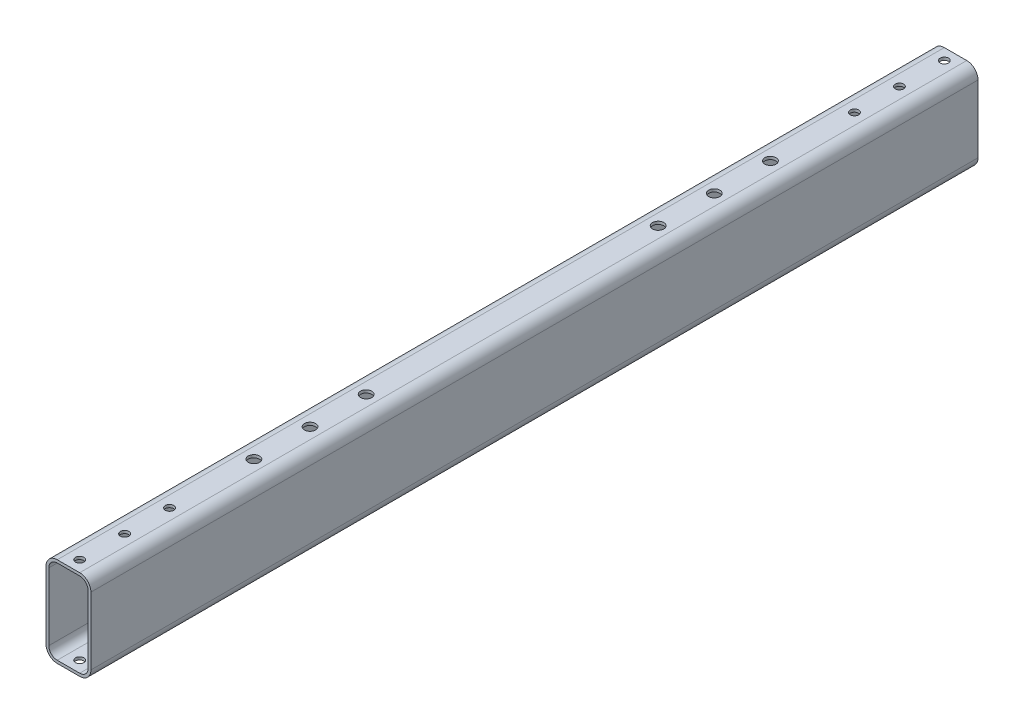
SolidWorks part; units mm, degrees
material "6061-T6 (SS)"
ref_plane "Front Plane" through (0, 0, 0) normal (0, 0, 1) x (1, 0, 0)
ref_plane "Top Plane" through (0, 0, 0) normal (0, 1, 0) x (1, 0, 0)
ref_plane "Right Plane" through (0, 0, 0) normal (1, 0, 0) x (0, 0, -1)
sketch "Sketch1" plane through (0, 0, 0) normal (0, 0, 1) x (1, 0, 0)
  line L1 (-6.35, -25.4) -> (6.35, -25.4)
  line L2 (-12.7, -19.05) -> (-12.7, 19.05)
  line L3 (-6.35, 25.4) -> (6.35, 25.4)
  line L4 (12.7, -19.05) -> (12.7, 19.05)
  line L5 (-12.7, -25.4) -> (12.7, 25.4) construction
  line L6 (-12.7, 25.4) -> (12.7, -25.4) construction
  arc A0 (-12.7, -19.05) -> (-6.35, -25.4) centre (-6.35, -19.05) ccw
  arc A1 (6.35, -25.4) -> (12.7, -19.05) centre (6.35, -19.05) ccw
  arc A2 (6.35, 25.4) -> (12.7, 19.05) centre (6.35, 19.05) cw
  arc A3 (-12.7, 19.05) -> (-6.35, 25.4) centre (-6.35, 19.05) cw
  point P0 (0, 0)
  dimension "D3" = 6.35
  dimension "D1" = 50.8
  dimension "D2" = 25.4
extrude "Extrude-Thin1" add sketch "Sketch1" along normal blind 501.65 thin thin type one direction reverse wall 1.5875
hole_wizard "3/16 (0.1875) Diameter Hole1" positions "3DSketch1" profile "Sketch3" hole size "3/16" standard "ANSI Inch" end condition through all
sketch3d "3DSketch1"
  line L1 (6.35, 25.4, 0) -> (-6.35, 25.4, 0) construction
  line L6 (0, 25.4, 501.65) -> (0, 25.4, 0) construction
  line L7 (6.35, 25.4, 501.65) -> (-6.35, 25.4, 501.65) construction
  point P57 (0, 25.4, 6.35)
  point P59 (0, 25.4, 31.75)
  point P61 (0, 25.4, 57.15)
  point P63 (0, 25.4, 469.9)
  point P65 (0, 25.4, 444.5)
  point P67 (0, 25.4, 495.3)
  dimension "D1" = 25.4
  dimension "D2" = 25.4
  dimension "D3" = 6.35
  dimension "D4" = 25.4
  dimension "D5" = 25.4
  dimension "D6" = 6.35
sketch "Sketch3" plane through (0, 25.4, 495.3) normal (1, 0, 0) x (0, 0, 1)
  line L0 (0, 0) -> (0, 50.8)
  line L1 (0, 50.8) -> (2.3812, 50.8)
  line L2 (2.3812, 50.8) -> (2.3812, 0)
  line L5 (2.3812, 0) -> (0, 0)
  line L11 (0, -6.35) -> (0, 107.95) construction
  dimension "Thru Hole Dia." = 4.7625
  dimension "Thru Hole Depth" = 50.8
hole_wizard "3/16 (0.195) Diameter Hole1" positions "Sketch4" profile "Sketch5" hole size "3/16" standard "ANSI Inch" end condition up to next
sketch "Sketch4" plane through (0, -25.4, 0) normal (0, -1, 0) x (-1, 0, 0)
  point P43 (-3.175, -69.85)
  point P46 (3.175, -95.25)
  point P49 (-3.175, -120.65)
  point P52 (3.175, -146.05)
  point P55 (-3.175, -171.45)
  point P58 (-3.175, -323.85)
  point P61 (3.175, -349.25)
  point P64 (-3.175, -374.65)
  point P67 (3.175, -400.05)
  point P70 (-3.175, -425.45)
sketch "Sketch5" plane through (3.175, -25.4, 69.85) normal (1, 0, 0) x (0, 0, -1)
  line L0 (0, 0) -> (0, 1.5875)
  line L1 (0, 1.5875) -> (2.4765, 1.5875)
  line L2 (2.4765, 1.5875) -> (2.4765, 0)
  line L5 (2.4765, 0) -> (0, 0)
  line L11 (0, -6.35) -> (0, 107.95) construction
  dimension "Thru Hole Dia." = 4.953
  dimension "Thru Hole Depth" = 1.5875
hole_wizard "1/4 (0.25) Diameter Hole1" positions "Sketch6" profile "Sketch7" hole size "1/4" standard "ANSI Inch"
sketch "Sketch6" plane through (0, 25.4, 0) normal (0, 1, 0) x (1, 0, 0)
  point P0 (0, -104.6752)
  point P3 (0, -136.4252)
  point P6 (0, -168.1752)
  point P9 (0, -396.8)
  point P12 (0, -365.05)
  point P15 (0, -333.3)
sketch "Sketch7" plane through (0, 25.4, 104.6752) normal (1, 0, 0) x (0, 0, 1)
  line L0 (0, 0) -> (0, 27.3077)
  line L1 (0, 27.3077) -> (3.175, 25.4)
  line L2 (3.175, 25.4) -> (3.175, 0)
  line L5 (3.175, 0) -> (0, 0)
  line L10 (0, 27.3077) -> (-3.175, 25.4) construction
  line L11 (0, -6.35) -> (0, 107.95) construction
  dimension "Hole Dia." = 6.35
  dimension "Hole Depth" = 25.4
  dimension "Drill Angle" = 118
